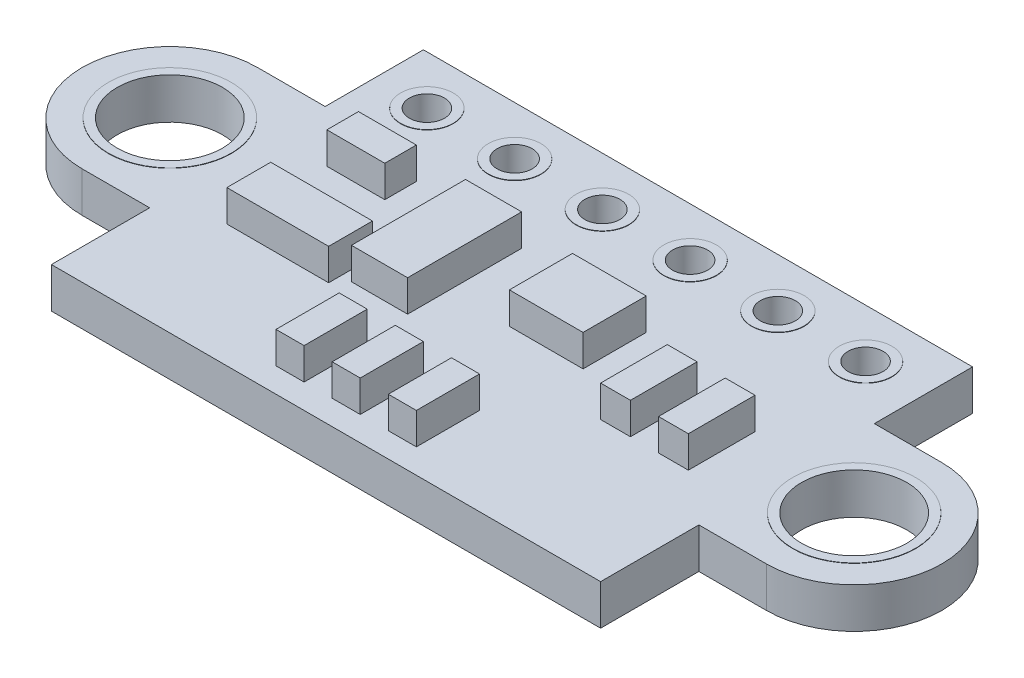
SolidWorks part; units mm, degrees
material "Copper"
ref_plane "Front Plane" through (0, 0, 0) normal (0, 0, 1) x (1, 0, 0)
ref_plane "Top Plane" through (0, 0, 0) normal (0, 1, 0) x (1, 0, 0)
ref_plane "Right Plane" through (0, 0, 0) normal (1, 0, 0) x (0, 0, -1)
sketch "Sketch1" plane through (0, 0, 0) normal (0, 1, 0) x (1, 0, 0)
  line L5 (-7.825, -5.3) -> (7.825, -5.3)
  line L6 (-7.825, -5.3) -> (-7.825, -2.5)
  line L7 (-7.825, 5.3) -> (7.825, 5.3)
  line L8 (7.825, -5.3) -> (7.825, -2.5)
  line L11 (9.75, 2.5) -> (7.825, 2.5)
  line L12 (9.75, -2.5) -> (7.825, -2.5)
  line L13 (-9.75, 2.5) -> (-7.825, 2.5)
  line L14 (-9.75, -2.5) -> (-7.825, -2.5)
  line L15 (-7.825, 2.5) -> (-7.825, 5.3)
  line L16 (7.825, 2.5) -> (7.825, 5.3)
  arc A0 (9.75, -2.5) -> (9.75, 2.5) centre (9.75, 0) ccw
  arc A1 (-9.75, -2.5) -> (-9.75, 2.5) centre (-9.75, 0) cw
  circle A2 centre (-9.75, 0) radius 1.5
  circle A3 centre (9.75, 0) radius 1.5
  point P0 (0, 0)
  dimension "D4" = 5
  dimension "D1" = 3
  dimension "D2" = 5
  dimension "D3" = 15.65
  dimension "D6" = 19.5
  dimension "D5" = 10.6
extrude "PCB" add sketch "Sketch1" along normal blind 1.15
sketch "Sketch2" plane through (0, 1.15, 0) normal (0, 1, 0) x (1, 0, 0)
  line L0 (-7.825, 3.9) -> (7.825, 3.9) construction
  line L1 (-7.825, 5.3) -> (-7.825, 2.5) construction
  line L2 (7.825, 2.5) -> (7.825, 5.3) construction
  circle A0 centre (-6.325, 3.9) radius 0.5
  dimension "D1" = 1
  dimension "D2" = 1.5
extrude "Initial Hole" cut sketch "Sketch2" against normal through all
pattern_linear "Pin Hole LPattern" count 6 spacing 2.5 along (1, 0, 0) of "Initial Hole"
sketch "Sketch4" plane through (0, 0, 0) normal (0, -1, 0) x (1, 0, 0)
  line L0 (-7.825, 2.5) -> (-7.825, 5.3) construction
  line L1 (-2.325, 3.7) -> (2.075, 3.7)
  line L2 (-2.325, 3.7) -> (-2.325, 1.3)
  line L3 (-2.325, 1.3) -> (2.075, 1.3)
  line L4 (2.075, 3.7) -> (2.075, 1.3)
  line L5 (-7.825, 5.3) -> (7.825, 5.3) construction
  dimension "D1" = 2.4
  dimension "D2" = 4.4
  dimension "D3" = 5.5
  dimension "D4" = 1.6
extrude "Bottom Component" add sketch "Sketch4" along normal blind 0.7
sketch "Sketch3" plane through (0, 1.15, 0) normal (0, 1, 0) x (1, 0, 0)
  line L0 (-1.325, -4.6) -> (-1.325, -2.8)
  line L1 (7.825, -5.3) -> (7.825, -2.5) construction
  line L2 (-6.325, -0.55) -> (-3.425, -0.55)
  line L3 (-6.325, -0.55) -> (-6.325, -1.8)
  line L4 (-6.325, -1.8) -> (-3.425, -1.8)
  line L5 (-2.125, -2.8) -> (-2.125, -4.6)
  line L6 (-3.425, -0.55) -> (-3.425, -1.8)
  line L7 (-2.125, -2.8) -> (-1.325, -2.8)
  line L8 (-2.125, -4.6) -> (-1.325, -4.6)
  line L9 (-7.825, -5.3) -> (7.825, -5.3) construction
  line L10 (-7.825, -2.5) -> (-7.825, -5.3) construction
  line L11 (-1.325, -2.8) -> (-0.525, -2.8) construction
  line L12 (0.275, -2.8) -> (1.075, -2.8) construction
  line L13 (-0.525, -2.8) -> (0.275, -2.8)
  line L14 (-0.525, -2.8) -> (-0.525, -4.6)
  line L15 (-0.525, -4.6) -> (0.275, -4.6)
  line L16 (0.275, -2.8) -> (0.275, -4.6)
  line L17 (-3.125, 1.8) -> (-1.525, 1.8)
  line L18 (1.075, -2.8) -> (1.875, -2.8)
  line L19 (1.075, -2.8) -> (1.075, -4.6)
  line L20 (1.075, -4.6) -> (1.875, -4.6)
  line L21 (1.875, -2.8) -> (1.875, -4.6)
  line L22 (-6.325, 1.95) -> (-4.675, 1.95)
  line L23 (-6.325, 1.95) -> (-6.325, 1.05)
  line L24 (-6.325, 1.05) -> (-4.675, 1.05)
  line L25 (-4.675, 1.95) -> (-4.675, 1.05)
  line L26 (-3.125, 1.8) -> (-3.125, -1.45)
  line L27 (-3.125, -1.45) -> (-1.525, -1.45)
  line L28 (-1.525, 1.8) -> (-1.525, -1.45)
  line L29 (0.225, 1.5) -> (2.325, 1.5)
  line L30 (0.225, 1.5) -> (0.225, -0.3)
  line L31 (0.225, -0.3) -> (2.325, -0.3)
  line L32 (2.325, 1.5) -> (2.325, -0.3)
  line L33 (3.825, 0.6) -> (4.675, 0.6)
  line L34 (3.825, 0.6) -> (3.825, -1.3)
  line L35 (3.825, -1.3) -> (4.675, -1.3)
  line L36 (4.675, 0.6) -> (4.675, -1.3)
  line L37 (5.475, 0.6) -> (6.325, 0.6)
  line L38 (5.475, 0.6) -> (5.475, -1.3)
  line L39 (5.475, -1.3) -> (6.325, -1.3)
  line L40 (6.325, 0.6) -> (6.325, -1.3)
  line L41 (7.825, 2.5) -> (7.825, 5.3) construction
  line L42 (-7.825, 5.3) -> (-7.825, 2.5) construction
  point P44 (-5.5, 1.95)
  dimension "D1" = 0.7
  dimension "D2" = 5.7
  dimension "D3" = 0.8
  dimension "D4" = 1.8
  dimension "D5" = 1.9
  dimension "D6" = 0.85
  dimension "D7" = 4
  dimension "D8" = 1.5
  dimension "D9" = 0.8
  dimension "D10" = 1.8
  dimension "D11" = 2.1
  dimension "D12" = 5.5
  dimension "D13" = 5
  dimension "D14" = 1.6
  dimension "D15" = 3.25
  dimension "D16" = 1.75
  dimension "D17" = 1.35
  dimension "D18" = 2.9
  dimension "D19" = 1.25
  dimension "D20" = 3.5
  dimension "D21" = 1.5
  dimension "D22" = 1.6
  dimension "D23" = 0.9
  dimension "D24" = 1.65
  dimension "D25" = 1.5
extrude "Tan Components" add sketch "Sketch3" along normal blind 0.9 contours L5 L8 L0 L7 | L16 L13 L14 L15 | L21 L18 L19 L20 | L25 L22 L23 L24 region at (-1.725, 1.15, 3.7) region at (-0.125, 1.15, 3.7) region at (1.475, 1.15, 3.7) region at (-5.5, 1.15, -1.5)
extrude "Black Components" add sketch "Sketch3<3>" along normal blind 0.9 contours L32 L29 L30 L31 | L28 L17 L26 L27 | L6 L2 L3 L4 | L36 L33 L34 L35 | L38 L39 L40 L37 region at (-4.875, 1.15, 1.175) region at (-2.325, 1.15, -0.175) region at (1.275, 1.15, -0.6) region at (4.25, 1.15, 0.35)
sketch "Sketch3<3>" plane through (0, 1.15, 0) normal (0, 1, 0) x (1, 0, 0) same geometry as "Sketch3"
sketch "Sketch5" plane through (0, 1.15, 0) normal (0, 1, 0) x (1, 0, 0)
  circle A0 centre (-9.75, 0) radius 1.75
  circle A1 centre (9.75, 0) radius 1.75
  circle A2 centre (-6.325, 3.9) radius 0.75
  circle A3 centre (-3.825, 3.9) radius 0.75
  circle A4 centre (-1.325, 3.9) radius 0.75
  circle A5 centre (1.175, 3.9) radius 0.75
  circle A6 centre (3.675, 3.9) radius 0.75
  circle A7 centre (6.175, 3.9) radius 0.75
  circle A8 centre (-6.325, 3.9) radius 0.5
  circle A9 centre (-3.825, 3.9) radius 0.5
  circle A10 centre (-1.325, 3.9) radius 0.5
  circle A11 centre (-1.325, 3.9) radius 0.5
  circle A12 centre (1.175, 3.9) radius 0.5
  circle A13 centre (3.675, 3.9) radius 0.5
  circle A14 centre (6.175, 3.9) radius 0.5
  circle A15 centre (-9.75, 0) radius 1.5
  circle A16 centre (9.75, 0) radius 1.5
  dimension "D1" = 3.5
  dimension "D2" = 1.5
  dimension "D3" = 1
  dimension "D4" = 3
extrude "Gold Contacts" add sketch "Sketch5" against normal offset from surface (1.17 mm away) 0.01 from offset 0.01 contours A2 A8 | A3 A9 | A4 A10 | A5 A12 | A6 A13 | A7 A14 | A0 A15 | A1 A16 region at (-11.4505, 1.15, 0) region at (8.0495, 1.15, 0) region at (-7.0538, 1.15, -3.9) region at (-4.5538, 1.15, -3.9) region at (-2.0538, 1.15, -3.9) region at (0.4462, 1.15, -3.9) region at (2.9462, 1.15, -3.9) region at (5.4462, 1.15, -3.9) up to face at (-3.825, 0, -3.4) offset beyond the face yes
sketch "Sketch6" plane through (0, 0, 0) normal (0, -1, 0) x (1, 0, 0)
  line L0 (-5.825, -2.8) -> (-5.825, 0.7) construction
  line L1 (-5.825, -2.8) -> (6.675, -2.8) construction
  line L2 (-3.325, -2.8) -> (-3.325, 0.7) construction
  line L3 (-0.825, -2.8) -> (-0.825, 0.7) construction
  line L4 (1.675, -2.8) -> (1.675, 0.7) construction
  line L5 (4.175, -2.8) -> (4.175, 0.7) construction
  line L6 (6.675, -2.8) -> (6.675, 0.7) construction
  line L8 (7.825, -5.3) -> (-7.825, -5.3) construction
  line L9 (7.825, -2.5) -> (7.825, -5.3) construction
  text T0 "VIN" font "Consolas" height 1
  text T1 "GND" font "Consolas" height 1
  text T2 "SCL" font "Consolas" height 1
  text T3 "SDA" font "Consolas" height 1
  text T4 "GPIO1" font "Consolas" height 1
  text T5 "XSHUT" font "Consolas" height 1
  dimension "D2" = 2.5
  dimension "D3" = 1.15
  dimension "D5" = 3.65
  dimension "D6" = 6.15
  dimension "D7" = 8.65
  dimension "D8" = 11.15
  dimension "D9" = 13.65
extrude "Silkscreen" add sketch "Sketch6" along normal blind 0.01
